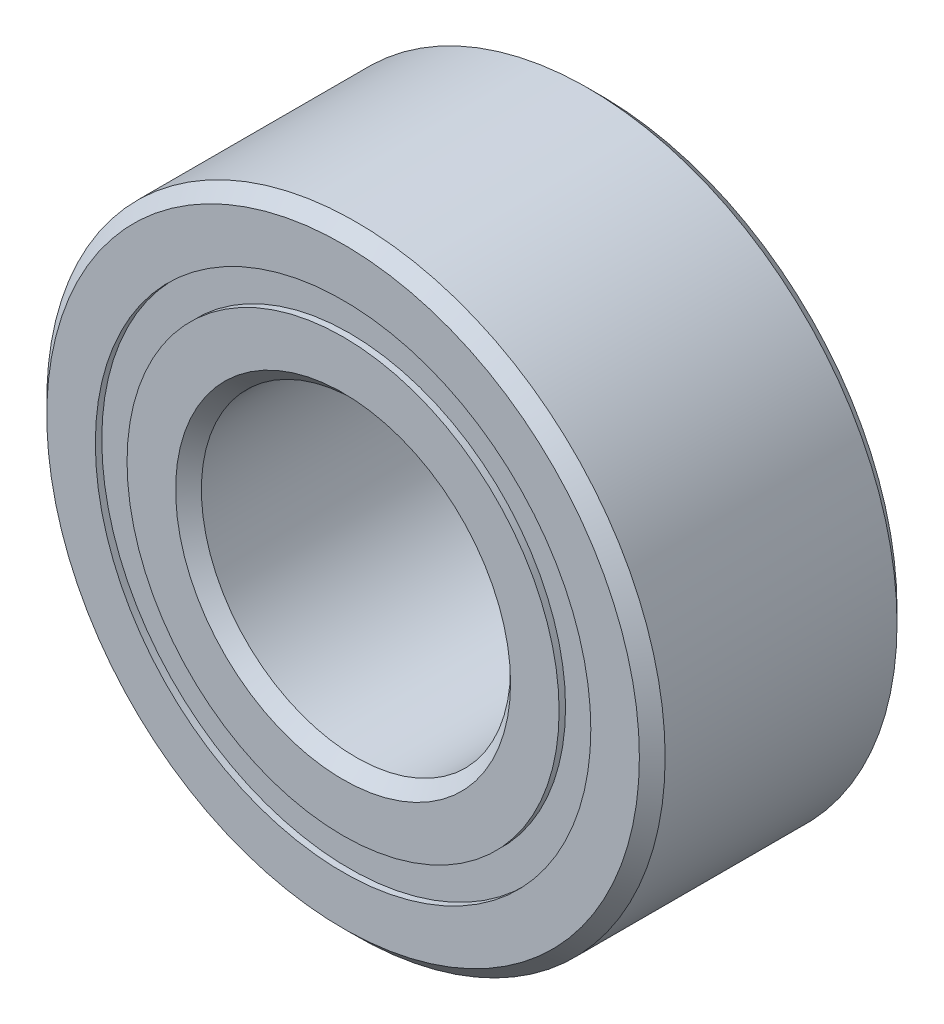
SolidWorks part; units mm, degrees
ref_plane "Front Plane" through (0, 0, 0) normal (0, 0, 1) x (1, 0, 0)
ref_plane "Top Plane" through (0, 0, 0) normal (0, 1, 0) x (1, 0, 0)
ref_plane "Right Plane" through (0, 0, 0) normal (1, 0, 0) x (0, 0, -1)
sketch "Sketch1" plane through (0, 0, 0) normal (1, 0, 0) x (0, 0, -1)
  line L0 (-1.25, 0) -> (1.25, 0) construction
  line L1 (0, 3) -> (0, -3) construction
  line L2 (1.125, 3) -> (-1.125, 3)
  line L3 (-1.125, 3) -> (-1.25, 2.875)
  line L4 (-1.25, 2.875) -> (-1.25, 2.4038)
  line L5 (-1.25, 2.4038) -> (-0.5556, 2.4038)
  line L6 (1.25, 2.4038) -> (0.5556, 2.4038)
  line L7 (1.25, 2.875) -> (1.25, 2.4038)
  line L8 (1.125, 3) -> (1.25, 2.875)
  line L9 (0, 3) -> (0, 2.25) construction
  line L10 (0, 2.25) -> (0, 1.5) construction
  arc A0 (-0.5556, 2.4038) -> (0.5556, 2.4038) centre (0, 2.25) cw
  point P14 (0, 1.5)
  dimension "Width" = 2.5
  dimension "OD" = 6
  dimension "D1" = 45
  dimension "D2" = 0.125
  dimension "Shaft Dia" = 3
  dimension "D3" = 1.1111
  dimension "D4" = 0.1538
revolve "Revolve1" add sketch "Sketch1" angle 360 about L0
sketch "Sketch3" plane through (0, 0, 0) normal (1, 0, 0) x (0, 0, -1)
  line L0 (-1.25, 2.0962) -> (-0.5556, 2.0962)
  line L1 (0, 3) -> (0, -3) construction
  line L2 (-1.25, 2.875) -> (-1.25, 2.4038) construction
  line L3 (-1.25, 2.0962) -> (-1.25, 1.625)
  line L4 (-1.125, 3) -> (-1.25, 2.875) construction
  line L5 (-1.25, 1.625) -> (-1.125, 1.5)
  line L6 (-1.125, 1.5) -> (1.125, 1.5)
  line L7 (1.125, 3) -> (1.125, -3) construction
  line L8 (1.125, 1.5) -> (1.25, 1.625)
  line L9 (1.25, -2.875) -> (1.25, 2.875) construction
  line L10 (1.25, 1.625) -> (1.25, 2.0962)
  line L11 (1.25, 2.0962) -> (0.5556, 2.0962)
  line L13 (1.125, 3) -> (1.25, 2.875) construction
  arc A0 (0.5556, 2.4038) -> (-0.5556, 2.4038) centre (0, 2.25) ccw construction
  arc A1 (0.5556, 2.0962) -> (-0.5556, 2.0962) centre (0, 2.25) cw
revolve "Revolve3" add sketch "Sketch3" angle 360 about L0
sketch "Sketch4" plane through (0, 0, 0) normal (1, 0, 0) x (0, 0, -1)
  line L0 (-0.5765, 2.25) -> (0.5765, 2.25)
  arc A2 (-0.5765, 2.25) -> (0.5765, 2.25) centre (0, 2.25) cw
  arc A3 (0.5556, 2.4038) -> (-0.5556, 2.4038) centre (0, 2.25) ccw construction
revolve "Revolve4" add sketch "Sketch4" angle 360 about L0
ref_axis "Axis1" through (0, 0, -1.25) along (0, 0, 1)
pattern_circular "CirPattern1" count 12 every 30 about axis through (0, 0, -1.25) along (0, 0, 1) of bodies 104
sketch "Sketch5" plane through (0, 0, 0) normal (1, 0, 0) x (0, 0, -1)
  line L0 (-1.25, 2.4038) -> (-0.5556, 2.4038) construction
  line L1 (-1.1875, 2.4038) -> (-0.5765, 2.4038)
  line L2 (-1.1875, 2.4038) -> (-1.1875, 2.0962)
  line L3 (-1.1875, 2.0962) -> (-0.5765, 2.0962)
  line L4 (-0.5765, 2.4038) -> (-0.5765, 2.0962)
  line L5 (-1.25, 2.0962) -> (-0.5556, 2.0962) construction
  line L6 (1.25, 2.4038) -> (0.5556, 2.4038) construction
  line L7 (1.1875, 2.4038) -> (0.5765, 2.4038)
  line L8 (1.1875, 2.4038) -> (1.1875, 2.0962)
  line L9 (1.1875, 2.0962) -> (0.5765, 2.0962)
  line L10 (0.5765, 2.4038) -> (0.5765, 2.0962)
  line L11 (1.25, 2.0962) -> (0.5556, 2.0962) construction
  line L12 (-1.125, 3) -> (-1.25, 2.875) construction
  point P18 (-1.1875, 2.9375)
revolve "Revolve5" add sketch "Sketch5" angle 360 about L0
sketch "Sketch6" plane through (0, 0, 0) normal (1, 0, 0) x (0, 0, -1)
  line L0 (1.25, 0) -> (-1.25, 0) construction
  line L1 (1.25, 2.4038) -> (0.15, 2.4038)
  line L2 (1.25, 2.4038) -> (1.25, 9.5)
  line L3 (1.25, 9.5) -> (0.15, 9.5)
  line L4 (0.15, 2.4038) -> (0.15, 9.5)
  dimension "Th" = 1.1
  dimension "Flange OD" = 19
revolve "Revolve6" [suppressed] add sketch "Sketch6" angle 360 about L0
equation "\"D2@Sketch1\" = \"Width@Sketch1\"*.05"
equation "\"D3@Sketch1\" = \"Width@Sketch1\"/2.25"
equation "\"D4@Sketch1\" = (((\"OD@Sketch1\"-\"Width@Sketch1\")/2)/3.25)/3.5"
equation "\"D2@CirPattern1\" = 360/\"Balls@CirPattern1\""
